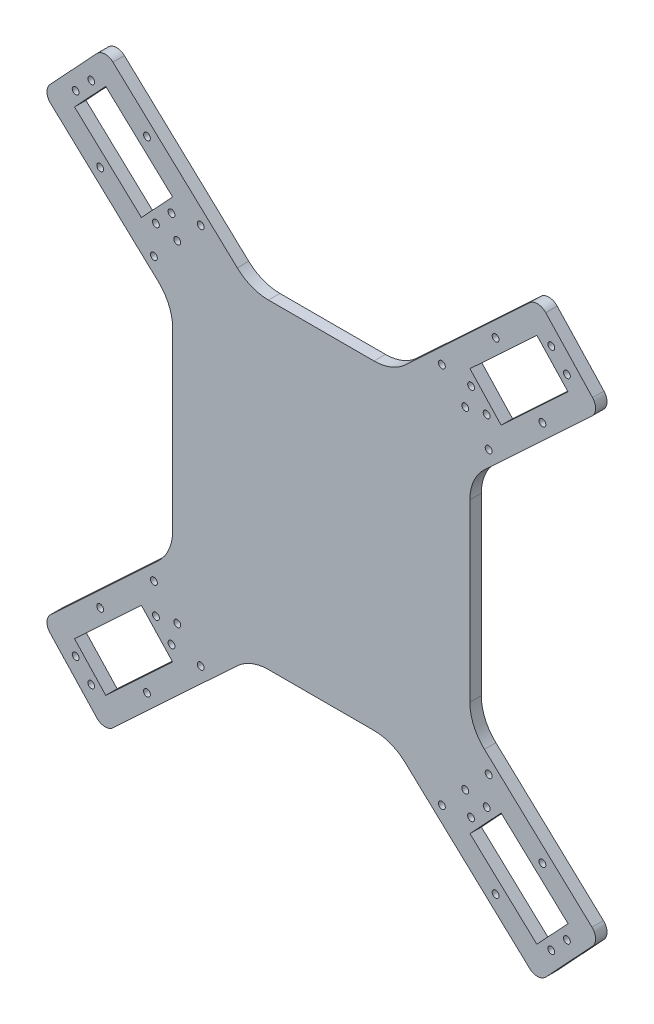
SolidWorks part; units mm, degrees
ref_plane "前视基准面" through (0, 0, 0) normal (0, 0, 1) x (1, 0, 0)
ref_plane "上视基准面" through (0, 0, 0) normal (0, 1, 0) x (1, 0, 0)
ref_plane "右视基准面" through (0, 0, 0) normal (1, 0, 0) x (0, 0, -1)
sketch "草图2" plane through (0, 0, 0) normal (0, 0, 1) x (1, 0, 0)
  line L0 (2886.4701, 1899.4965) -> (2857.2159, 1872.2166)
  line L1 (2857.2159, 1872.2166) -> (2870.8559, 1857.5895)
  line L2 (2870.8559, 1857.5895) -> (2900.1101, 1884.8695)
  line L3 (2886.4701, 1899.4965) -> (2900.1101, 1884.8695)
  line L4 (2769.0664, 1854.1359) -> (2815.2858, 1854.1359)
  line L5 (2857.1761, 1822.4634) -> (2857.1761, 1745.8085)
  line L6 (2815.2858, 1714.1359) -> (2769.0664, 1714.1359)
  line L7 (2727.1761, 1745.8085) -> (2727.1761, 1822.4634)
  line L8 (2697.8821, 1899.4965) -> (2727.1362, 1872.2166)
  line L9 (2727.1362, 1872.2166) -> (2713.4963, 1857.5895)
  line L10 (2713.4963, 1857.5895) -> (2684.2421, 1884.8695)
  line L11 (2697.8821, 1899.4965) -> (2684.2421, 1884.8695)
  line L12 (2886.4701, 1668.7753) -> (2857.2159, 1696.0552)
  line L13 (2857.2159, 1696.0552) -> (2870.8559, 1710.6823)
  line L14 (2870.8559, 1710.6823) -> (2900.1101, 1683.4024)
  line L15 (2886.4701, 1668.7753) -> (2900.1101, 1683.4024)
  line L16 (2697.8821, 1668.7753) -> (2727.1362, 1696.0552)
  line L17 (2727.1362, 1696.0552) -> (2713.4963, 1710.6823)
  line L18 (2713.4963, 1710.6823) -> (2684.2421, 1683.4024)
  line L19 (2697.8821, 1668.7753) -> (2684.2421, 1683.4024)
  line L20 (2720.8161, 1837.0904) -> (2673.7654, 1880.9659)
  line L21 (2755.4264, 1859.5088) -> (2701.0453, 1910.2201)
  line L22 (2693.9785, 1909.9733) -> (2673.5186, 1888.0327)
  line L23 (2863.5361, 1837.0904) -> (2910.5868, 1880.9659)
  line L24 (2828.9258, 1859.5088) -> (2883.3069, 1910.2201)
  line L25 (2890.3736, 1909.9733) -> (2910.8336, 1888.0327)
  line L26 (2720.8161, 1731.1814) -> (2673.7654, 1687.3059)
  line L27 (2755.4264, 1708.763) -> (2701.0453, 1658.0518)
  line L28 (2693.9785, 1658.2986) -> (2673.5186, 1680.2392)
  line L29 (2863.5361, 1731.1814) -> (2910.5868, 1687.3059)
  line L30 (2828.9258, 1708.763) -> (2883.3069, 1658.0518)
  line L31 (2890.3736, 1658.2986) -> (2910.8336, 1680.2392)
  circle A0 centre (2892.8055, 1898.5678) radius 1.5
  circle A1 centre (2899.6255, 1891.2542) radius 1.5
  circle A2 centre (2857.7005, 1865.8318) radius 1.5
  circle A3 centre (2864.5205, 1858.5183) radius 1.5
  arc A4 (2857.1761, 1745.8085) -> (2863.5361, 1731.1814) centre (2877.1761, 1745.8085) ccw
  arc A5 (2769.0664, 1714.1359) -> (2755.4264, 1708.763) centre (2769.0664, 1694.1359) ccw
  arc A6 (2727.1761, 1822.4634) -> (2720.8161, 1837.0904) centre (2707.1761, 1822.4634) ccw
  circle A7 centre (2691.5467, 1898.5678) radius 1.5
  circle A8 centre (2684.7267, 1891.2542) radius 1.5
  circle A9 centre (2726.6517, 1865.8318) radius 1.5
  circle A10 centre (2719.8317, 1858.5183) radius 1.5
  circle A11 centre (2892.8055, 1669.7041) radius 1.5
  circle A12 centre (2899.6255, 1677.0176) radius 1.5
  circle A13 centre (2857.7005, 1702.44) radius 1.5
  circle A14 centre (2864.5205, 1709.7535) radius 1.5
  circle A15 centre (2691.5467, 1669.7041) radius 1.5
  circle A16 centre (2684.7267, 1677.0176) radius 1.5
  circle A17 centre (2726.6517, 1702.44) radius 1.5
  circle A18 centre (2719.8317, 1709.7535) radius 1.5
  arc A19 (2755.4264, 1859.5088) -> (2769.0664, 1854.1359) centre (2769.0664, 1874.1359) ccw
  arc A20 (2701.0453, 1910.2201) -> (2693.9785, 1909.9733) centre (2697.6353, 1906.5633) ccw
  arc A21 (2673.5186, 1888.0327) -> (2673.7654, 1880.9659) centre (2677.1754, 1884.6227) ccw
  arc A22 (2863.5361, 1837.0904) -> (2857.1761, 1822.4634) centre (2877.1761, 1822.4634) ccw
  arc A23 (2910.5868, 1880.9659) -> (2910.8336, 1888.0327) centre (2907.1768, 1884.6227) ccw
  arc A24 (2815.2858, 1854.1359) -> (2828.9258, 1859.5088) centre (2815.2858, 1874.1359) ccw
  arc A25 (2890.3736, 1909.9733) -> (2883.3069, 1910.2201) centre (2886.7169, 1906.5633) ccw
  arc A26 (2720.8161, 1731.1814) -> (2727.1761, 1745.8085) centre (2707.1761, 1745.8085) ccw
  arc A27 (2693.9785, 1658.2986) -> (2701.0453, 1658.0518) centre (2697.6353, 1661.7085) ccw
  arc A28 (2673.7654, 1687.3059) -> (2673.5186, 1680.2392) centre (2677.1754, 1683.6492) ccw
  arc A29 (2828.9258, 1708.763) -> (2815.2858, 1714.1359) centre (2815.2858, 1694.1359) ccw
  arc A30 (2883.3069, 1658.0518) -> (2890.3736, 1658.2986) centre (2886.7169, 1661.7085) ccw
  arc A31 (2910.8336, 1680.2392) -> (2910.5868, 1687.3059) centre (2907.1768, 1683.6492) ccw
extrude "凸台-拉伸1" add sketch "草图2" along normal blind 5 contours A6 L20 A21 L22 A20 L21 A19 L4 A24 L24 A25 L25 A23 L23 A22 L5 A4 L29 A31 L31 A30 L30 A29 L6 A5 L27 A27 L28 A28 L26 A26 L7
extrude "切除-拉伸1" cut sketch "草图2<3>" along normal blind 5 contours A1 | A0 | A2 | A3 | A11 | A14 | A13 | L19 L16 L17 L18 | L12 L15 L14 L13 | L8 L11 L10 L9 | A7 | L2 L3 L0 L1 | A12 | A17 | A18 | A15 | A16 | A9 | A10 | A8 region at (2705.6892, 1878.543, 0) region at (2878.663, 1689.7288, 0) region at (2705.6892, 1689.7288, 0) region at (2892.8055, 1898.5678, 0) region at (2899.6255, 1891.2542, 0) region at (2857.7005, 1865.8318, 0) region at (2864.5205, 1858.5183, 0) region at (2691.5467, 1898.5678, 0) region at (2892.8055, 1669.7041, 0) region at (2857.7005, 1702.44, 0) region at (2864.5205, 1709.7535, 0)
sketch "草图2<3>" plane through (0, 0, 0) normal (0, 0, 1) x (1, 0, 0) same geometry as "草图2"
sketch "草图3" plane through (0, 0, 0) normal (0, 0, -1) x (-1, 0, 0)
  circle A0 centre (-2888.893, 1700.6991) radius 1.5
  circle A1 centre (-2868.433, 1678.7585) radius 1.5
  circle A2 centre (-2715.9192, 1678.7585) radius 1.5
  circle A3 centre (-2695.4592, 1700.6991) radius 1.5
  circle A4 centre (-2695.4592, 1867.5727) radius 1.5
  circle A5 centre (-2715.9192, 1889.5133) radius 1.5
  circle A6 centre (-2868.433, 1889.5133) radius 1.5
  circle A7 centre (-2888.893, 1867.5727) radius 1.5
extrude "切除-拉伸2" cut sketch "草图3" against normal blind 10
sketch "草图4" plane through (0, 0, 0) normal (0, 0, -1) x (-1, 0, 0)
  circle A0 centre (-2865.3919, 1722.6142) radius 1.5
  circle A1 centre (-2855.1619, 1711.6439) radius 1.5
  circle A2 centre (-2844.9319, 1700.6736) radius 1.5
  circle A3 centre (-2739.4203, 1700.6736) radius 1.5
  circle A4 centre (-2729.1903, 1711.6439) radius 1.5
  circle A5 centre (-2718.9603, 1722.6142) radius 1.5
  circle A6 centre (-2718.9603, 1845.6576) radius 1.5
  circle A7 centre (-2729.1903, 1856.6279) radius 1.5
  circle A8 centre (-2739.4203, 1867.5982) radius 1.5
  circle A9 centre (-2844.9319, 1867.5982) radius 1.5
  circle A10 centre (-2855.1619, 1856.6279) radius 1.5
  circle A11 centre (-2865.3919, 1845.6576) radius 1.5
extrude "切除-拉伸3" cut sketch "草图4" against normal blind 33
